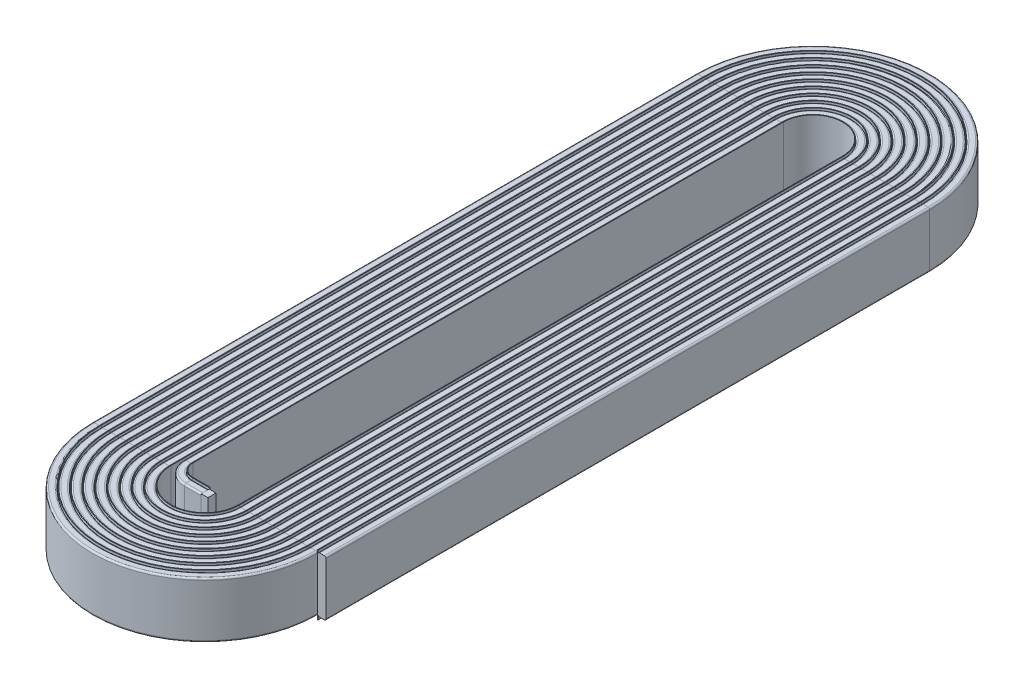
SolidWorks part; units mm, degrees
ref_plane "Спереди" through (0, 0, 0) normal (0, 0, 1) x (1, 0, 0)
ref_plane "Сверху" through (0, 0, 0) normal (0, 1, 0) x (1, 0, 0)
ref_plane "Справа" through (0, 0, 0) normal (1, 0, 0) x (0, 0, -1)
sketch "Траектория намотки" plane through (0, 0, 0) normal (0, 1, 0) x (1, 0, 0)
  line L0 (4.5, 0) -> (4.5, 90)
  line L1 (-16.2, 0) -> (-16.2, 90)
  line L2 (-14.9, 90) -> (-14.9, 0)
  line L3 (-5.8, 90) -> (-5.8, 0)
  line L4 (-13.6, 90) -> (-13.6, 0)
  line L5 (0, 0) -> (-2.5, 0)
  line L6 (-12.3, 90) -> (-12.3, 0)
  line L7 (-11, 90) -> (-11, 0)
  line L8 (-9.7, 0) -> (-9.7, 90)
  line L9 (-8.4, 90) -> (-8.4, 0)
  line L10 (-7.1, 0) -> (-7.1, 90)
  line L12 (-4.5, 2) -> (-4.5, 90)
  line L13 (5.8, 0) -> (5.8, 90)
  line L14 (7.1, 90) -> (7.1, 0)
  line L15 (8.4, 0) -> (8.4, 90)
  line L16 (9.7, 90) -> (9.7, 0)
  line L17 (11, 90) -> (11, 0)
  line L18 (12.3, 90) -> (12.3, 0)
  line L19 (13.6, 0) -> (13.6, 90)
  line L20 (14.9, 90) -> (14.9, 0)
  line L21 (16.2, 0) -> (16.2, 90)
  arc A1 (-5.8, 90) -> (5.8, 90) centre (0, 90) cw
  arc A2 (-7.1, 90) -> (7.1, 90) centre (0, 90) cw
  arc A3 (-8.4, 90) -> (8.4, 90) centre (0, 90) cw
  arc A4 (-9.7, 90) -> (9.7, 90) centre (0, 90) cw
  arc A5 (-11, 90) -> (11, 90) centre (0, 90) cw
  arc A6 (-12.3, 90) -> (12.3, 90) centre (0, 90) cw
  arc A7 (-13.6, 90) -> (13.6, 90) centre (0, 90) cw
  arc A8 (-14.9, 90) -> (14.9, 90) centre (0, 90) cw
  arc A9 (-16.2, 90) -> (16.2, 90) centre (0, 90) cw
  arc A12 (4.5, 0) -> (-5.8, 0) centre (-0.65, 0) cw
  arc A13 (5.8, 0) -> (-7.1, 0) centre (-0.65, 0) cw
  arc A14 (7.1, 0) -> (-8.4, 0) centre (-0.65, 0) cw
  arc A15 (8.4, 0) -> (-9.7, 0) centre (-0.65, 0) cw
  arc A16 (9.7, 0) -> (-11, 0) centre (-0.65, 0) cw
  arc A17 (11, 0) -> (-12.3, 0) centre (-0.65, 0) cw
  arc A18 (12.3, 0) -> (-13.6, 0) centre (-0.65, 0) cw
  arc A19 (13.6, 0) -> (-14.9, 0) centre (-0.65, 0) cw
  arc A20 (14.9, 0) -> (-16.2, 0) centre (-0.65, 0) cw
  arc A21 (4.5, 90) -> (-4.5, 90) centre (0, 90) ccw
  arc A22 (-4.5, 2) -> (-2.5, 0) centre (-2.5, 2) ccw
  dimension "D1" = 2
sketch "Сечение провода обмотки" plane through (0, 0, 0) normal (1, 0, 0) x (0, 0, -1)
  line L5 (-0.25, 0) -> (-0.95, 0)
  line L6 (0, 0.25) -> (0, 8.05)
  line L7 (-0.25, 8.3) -> (-0.95, 8.3)
  line L8 (-1.2, 0.25) -> (-1.2, 8.05)
  arc A4 (-0.95, 0) -> (-1.2, 0.25) centre (-0.95, 0.25) cw
  arc A5 (0, 8.05) -> (-0.25, 8.3) centre (-0.25, 8.05) ccw
  arc A6 (-0.95, 8.3) -> (-1.2, 8.05) centre (-0.95, 8.05) ccw
  arc A7 (-0.25, 0) -> (0, 0.25) centre (-0.25, 0.25) ccw
  point P12 (0, 0)
  dimension "D1" = 0.25
sweep "По траектории5" add profiles "Сечение провода обмотки" path "Траектория намотки"
sketch "Эскиз1" plane through (0, 0, 0) normal (1, 0, 0) x (0, 0, -1)
  line L1 (0.1, 8.5) -> (0, 8.5)
  line L2 (0.1, 8.5) -> (0.1, -0.5)
  line L3 (0.1, -0.5) -> (0, -0.5)
  line L4 (0, 8.5) -> (0, -0.5)
sweep "По траектории6" add profiles "Эскиз1" path "Траектория намотки<2>"
sketch "Траектория намотки<2>" plane through (0, 0, 0) normal (0, 1, 0) x (1, 0, 0) same geometry as "Траектория намотки"
sketch "Эскиз3" plane through (0, 0, 0) normal (1, 0, 0) x (0, 0, -1)
  line L1 (-1.2, 8.3) -> (0, 8.3)
  line L2 (-1.2, 8.3) -> (-1.2, 0)
  line L3 (-1.2, 0) -> (0, 0)
  line L4 (0, 8.3) -> (0, 0)
  point P4 (0, 0)
  point P5 (0, 0)
  point P6 (0, 8.275)
  point P10 (0, 0)
  point P11 (0, 0)
  point P12 (0, 0)
  point P13 (0, 0)
  point P14 (0, 0)
  point P15 (0, 0)
  point P16 (0, 0)
  point P17 (-1.1997, 8.3059)
  point P18 (0, 0)
sheet metal parameters "Листовой металл1" thickness 1 parameters "D1"=0.7366, "Толщина"=1
base flange "Базовая кромка1" sketch "Эскиз3" thickness 1 reverse thickness direction yes parameters "D1"=0.7366
sketch "Эскиз21" plane through (0, 0, 0) normal (0, 0, -1) x (-1, 0, 0)
  line L0 (-1, 8.3) -> (0, 8.3) construction
  line L1 (-0.5, 8.3) -> (-0.5, 0)
  line L2 (-1, 0) -> (0, 0) construction
flat pattern "Развертка1" [suppressed]
sketch "Сгиб-Линии1" plane through (0, 0, 0) normal (0, 1, 0) x (1, 0, 0)
sketch3d "Граничная рамка1" [suppressed]
  line L0 (0, 8.3, 0) -> (0, 0, 0) construction
  line L1 (-1.2, 8.3, 0) -> (-1.2, 0, 0) construction
  line L2 (0, 8.3, 0) -> (-1.2, 8.3, 0) construction
  line L3 (0, 0, 0) -> (-1.2, 0, 0) construction
